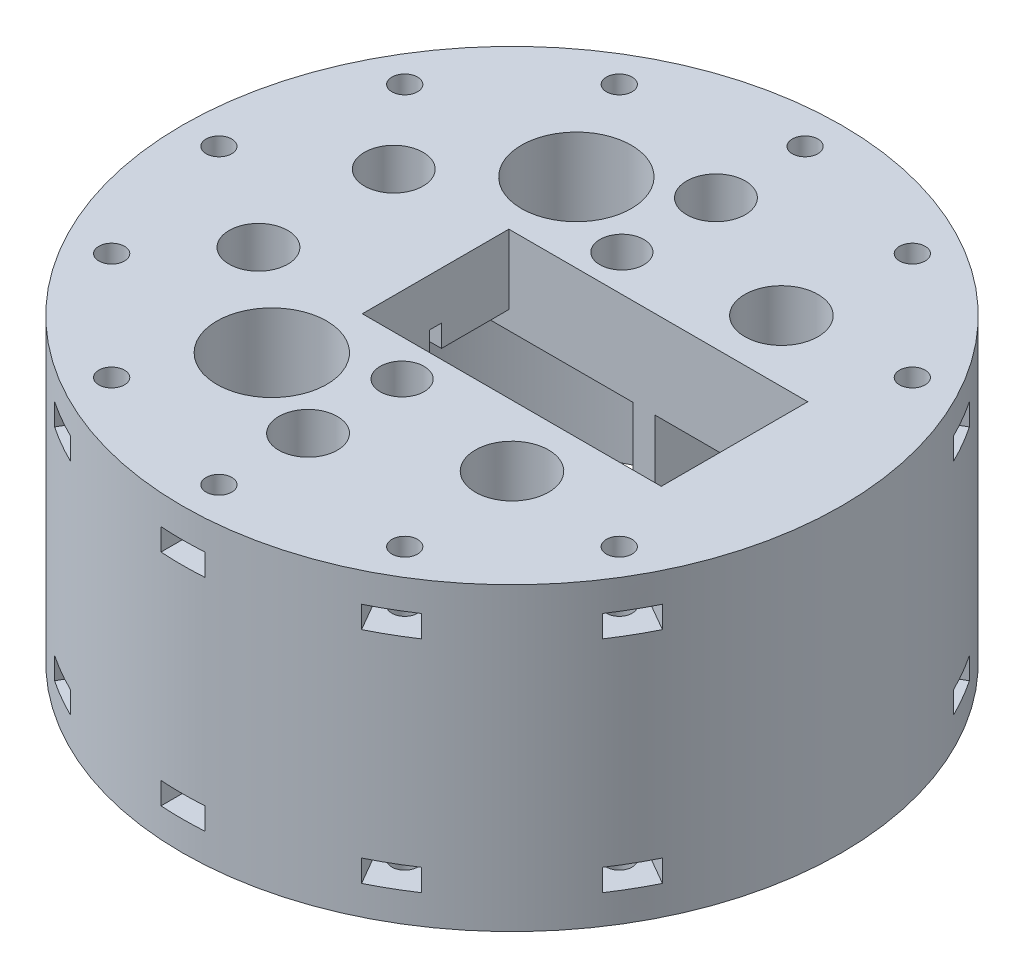
SolidWorks part; units mm, degrees
ref_plane "Front Plane" through (0, 0, 0) normal (0, 0, 1) x (1, 0, 0)
ref_plane "Top Plane" through (0, 0, 0) normal (0, 1, 0) x (1, 0, 0)
ref_plane "Right Plane" through (0, 0, 0) normal (1, 0, 0) x (0, 0, -1)
sketch "Sketch1" plane through (0, 0, 0) normal (0, 1, 0) x (1, 0, 0)
  line L0 (-43.0464, 0) -> (41.9462, 0) construction
  line L1 (0, 43.1152) -> (0, -41.8775) construction
  circle A1 centre (0, 0) radius 45
  dimension "D2" = 90
extrude "Boss-Extrude1" add sketch "Sketch1" along normal blind 41
sketch "Sketch2" plane through (0, 0, 0) normal (0, -1, 0) x (1, 0, 0)
  circle A0 centre (0, 0) radius 35
  dimension "D1" = 70
extrude "Cut-Extrude1" cut sketch "Sketch2" against normal blind 29
sketch "Sketch3" plane through (0, 29, 0) normal (0, -1, 0) x (1, 0, 0)
  line L0 (35, 0) -> (-35, 0) construction
  line L1 (0, -35) -> (0, 35) construction
  line L3 (37.5324, -10) -> (-17.4676, -10)
  line L4 (37.5324, -10) -> (37.5324, 10)
  line L5 (37.5324, 10) -> (-17.4676, 10)
  line L6 (-17.4676, -10) -> (-17.4676, 10)
  circle A0 centre (0, 0) radius 35 construction
  circle A1 centre (0, 0) radius 35 construction
  dimension "D1" = 20
  dimension "D2" = 55
  dimension "D3" = 10
  dimension "D4" = 37.5324
extrude "Cut-Extrude2" cut sketch "Sketch3" against normal blind 2.5 and the other way up to next
sketch "Sketch4" plane through (0, 31.5, 0) normal (0, -1, 0) x (1, 0, 0)
  line L0 (37.5324, 0) -> (-17.4676, 0) construction
  line L1 (37.5324, 10) -> (37.5324, -10) construction
  line L2 (-17.4676, 10) -> (-17.4676, -10) construction
  line L3 (0, -10) -> (0, 10) construction
  line L4 (-17.4676, -10) -> (33.541, -10) construction
  line L5 (33.541, 10) -> (-17.4676, 10) construction
  line L7 (30.3722, -10) -> (-10.4278, -10)
  line L8 (30.3722, -10) -> (30.3722, 10)
  line L9 (30.3722, 10) -> (-10.4278, 10)
  line L10 (-10.4278, -10) -> (-10.4278, 10)
  dimension "D1" = 20
  dimension "D2" = 40.8
  dimension "D3" = 30.3722
  dimension "D4" = 10
extrude "Cut-Extrude3" cut sketch "Sketch4" against normal blind 10.5
sketch "Sketch8" plane through (0, 29, 0) normal (0, -1, 0) x (1, 0, 0)
  line L0 (-17.4676, 0) -> (-35, 0) construction
  line L1 (-17.4676, 10) -> (-17.4676, -10) construction
  line L2 (8.0367, 10) -> (8.0367, 34.0648) construction
  line L3 (33.541, 10) -> (-17.4676, 10) construction
  line L4 (8.0367, -10) -> (8.0367, -29.3194) construction
  line L5 (-17.4676, -10) -> (33.541, -10) construction
  line L6 (6.5367, 10) -> (6.5367, 34.3842)
  line L7 (9.5367, 10) -> (9.5367, 33.6757)
  line L8 (9.5367, 10) -> (6.5367, 10)
  line L9 (9.5367, -10) -> (6.5367, -10)
  line L10 (6.5367, -10) -> (6.5367, -34.3842)
  line L11 (9.5367, -10) -> (9.5367, -33.6757)
  line L12 (-17.4676, 1.5) -> (-34.9678, 1.5)
  line L13 (-17.4676, -1.5) -> (-34.9678, -1.5)
  line L14 (-17.4676, 1.5) -> (-17.4676, -1.5)
  arc A0 (33.541, 10) -> (33.541, -10) centre (0, 0) ccw construction
  arc A1 (9.5367, 33.6757) -> (6.5367, 34.3842) centre (7.9531, 33.6757) ccw
  arc A2 (9.5367, -33.6757) -> (6.5367, -34.3842) centre (7.9531, -33.6757) cw
  arc A3 (-34.9678, 1.5) -> (-34.9678, -1.5) centre (-34.9678, 0) ccw
  dimension "D3" = 1.5
  dimension "D1" = 1.5
  dimension "D2" = 1.5
  dimension "D4" = 1.5
extrude "Boss-Extrude2" add sketch "Sketch8" along normal through all
sketch "Sketch13" plane through (0, 29, 0) normal (0, -1, 0) x (1, 0, 0)
  line L0 (0, 0) -> (0, 35) construction
  line L1 (0, 0) -> (-17.5, 30.3109) construction
  line L2 (0, 0) -> (-41.2446, 0) construction
  line L3 (-32.8892, 11.9707) -> (0, 0) construction
  line L5 (0, 0) -> (24.7487, 24.7487) construction
  arc A0 (6.5367, 34.3842) -> (-34.9678, 1.5) centre (0, 0) ccw construction
  circle A1 centre (-12, 20.7846) radius 7.5
  circle A2 centre (-25.3717, 9.2345) radius 4
  arc A3 (33.541, 10) -> (9.5367, 33.6757) centre (0, 0) ccw construction
  circle A4 centre (18.3848, 18.3848) radius 5
  circle A5 centre (18.3848, -18.3848) radius 5
  circle A6 centre (-12, -20.7846) radius 7.5
  circle A7 centre (-25.3717, -9.2345) radius 4
  circle A8 centre (0, -15) radius 3
  circle A9 centre (0, -27.8351) radius 4
  circle A10 centre (0, 27.8351) radius 4
  circle A11 centre (0, 15) radius 3
  dimension "D3" = 15
  dimension "D6" = 8
  dimension "D8" = 10
  dimension "D10" = 8
  dimension "D11" = 6
  dimension "D1" = 30
  dimension "D2" = 20
  dimension "D4" = 27
  dimension "D5" = 24
  dimension "D7" = 45
  dimension "D9" = 26
  dimension "D12" = 15
extrude "Cut-Extrude7" cut sketch "Sketch13" against normal through all
sketch "Sketch15" plane through (0, 0, -1.5) normal (0, 0, -1) x (-1, 0, 0)
  line L0 (34.9678, 0) -> (17.4676, 29)
  line L1 (17.4676, 29) -> (17.4676, 0)
  line L3 (17.4676, 0) -> (34.9678, 0)
extrude "Cut-Extrude8" cut sketch "Sketch15" against normal blind 3
sketch "Sketch16" plane through (0, 31.5, 0) normal (0, -1, 0) x (1, 0, 0)
  line L0 (-17.4676, 0) -> (37.5324, 0) construction
  line L1 (-17.4676, 10) -> (-17.4676, -10) construction
  line L2 (37.5324, -10) -> (37.5324, 10) construction
  line L3 (30.3722, -0.8) -> (37.5324, -0.8)
  line L4 (-10.4278, -0.8) -> (-17.4676, -0.8)
  line L5 (-10.4278, 10) -> (-10.4278, -10) construction
  line L6 (-10.4278, 0.8) -> (-17.4676, 0.8)
  line L7 (-17.4676, 0.8) -> (-17.4676, -0.8)
  line L8 (-10.4278, 0.8) -> (-10.4278, -0.8)
  line L9 (30.3722, -10) -> (30.3722, 10) construction
  line L10 (30.3722, 0.8) -> (37.5324, 0.8)
  line L11 (37.5324, 0.8) -> (37.5324, -0.8)
  line L12 (30.3722, 0.8) -> (30.3722, -0.8)
  dimension "D1" = 0.8
extrude "Cut-Extrude10" cut sketch "Sketch16" against normal blind 3
sketch "Sketch27" plane through (0, 0, 0) normal (0, -1, 0) x (1, 0, 0)
  line L0 (0, 0) -> (0, -53.17) construction
  line L1 (0, 0) -> (47.7582, -27.5732) construction
  line L3 (31.641, -18.2679) -> (31.641, -21.7321) construction
  line L4 (31.641, -21.7321) -> (34.641, -23.4641) construction
  line L5 (34.641, -23.4641) -> (37.641, -21.7321) construction
  line L6 (37.641, -21.7321) -> (37.641, -18.2679) construction
  line L7 (37.641, -18.2679) -> (34.641, -16.5359) construction
  line L8 (34.641, -16.5359) -> (31.641, -18.2679) construction
  circle A0 centre (0, 0) radius 40 construction
  circle A1 centre (34.641, -20) radius 1.75
  circle A2 centre (0, 0) radius 35 construction
  circle A3 centre (34.641, -20) radius 3 construction
  circle A4 centre (20, -34.641) radius 1.75
  circle A5 centre (0, -40) radius 1.75
  circle A6 centre (-20, -34.641) radius 1.75
  circle A7 centre (-34.641, -20) radius 1.75
  circle A8 centre (-40, 0) radius 1.75
  circle A9 centre (-34.641, 20) radius 1.75
  circle A10 centre (-20, 34.641) radius 1.75
  circle A11 centre (0, 40) radius 1.75
  circle A12 centre (20, 34.641) radius 1.75
  circle A13 centre (34.641, 20) radius 1.75
  circle A15 centre (40, 0) radius 1.75 [skipped]
  point P28 (0, 0)
  point P41 (0, 0)
  dimension "D1" = 80
  dimension "D3" = 3.5
  dimension "D4" = 70
  dimension "D5" = 6
  dimension "D6" = 12
  dimension "D2" = 60
extrude "Cut-Extrude15" cut sketch "Sketch27" against normal through all
ref_plane "Plane1" through (0, 37, 0) normal (0, 1, 0) x (1, 0, 0)
sketch "Sketch28" plane through (0, 37, 0) normal (0, 1, 0) x (1, 0, 0)
  line L0 (0, 0) -> (-54.493, 0) construction
  line L1 (-31.641, 18.2679) -> (-31.641, 21.7321)
  line L2 (-36.5359, 0) -> (-38.2679, 3)
  line L3 (-38.2679, 3) -> (-44.8999, 3)
  line L4 (-31.641, 21.7321) -> (-37.3844, 25.048)
  line L5 (-40.3844, 19.8519) -> (-34.641, 16.5359)
  line L6 (-44.8999, -3) -> (-38.2679, -3)
  line L7 (-38.2679, -3) -> (-36.5359, 0)
  line L8 (-43.4641, 0) -> (-42.5981, -1.5) [skipped]
  line L9 (-41.7321, 3) -> (-42.5981, 1.5) [skipped]
  line L10 (-34.641, 16.5359) -> (-31.641, 18.2679)
  line L11 (-18.2679, 31.641) -> (-16.5359, 34.641)
  line L12 (-16.5359, 34.641) -> (-19.8519, 40.3844)
  line L13 (-25.048, 37.3844) -> (-21.7321, 31.641)
  line L14 (-21.7321, 31.641) -> (-18.2679, 31.641)
  line L15 (0, 36.5359) -> (3, 38.2679)
  line L16 (3, 38.2679) -> (3, 44.8999)
  line L17 (-3, 44.8999) -> (-3, 38.2679)
  line L18 (-3, 38.2679) -> (0, 36.5359)
  line L19 (18.2679, 31.641) -> (21.7321, 31.641)
  line L20 (21.7321, 31.641) -> (25.048, 37.3844)
  line L21 (19.8519, 40.3844) -> (16.5359, 34.641)
  line L22 (16.5359, 34.641) -> (18.2679, 31.641)
  line L23 (31.641, 18.2679) -> (34.641, 16.5359)
  line L24 (34.641, 16.5359) -> (40.3844, 19.8519)
  line L25 (37.3844, 25.048) -> (31.641, 21.7321)
  line L26 (31.641, 21.7321) -> (31.641, 18.2679)
  line L31 (31.641, -18.2679) -> (31.641, -21.7321)
  line L32 (31.641, -21.7321) -> (37.3844, -25.048)
  line L33 (40.3844, -19.8519) -> (34.641, -16.5359)
  line L34 (34.641, -16.5359) -> (31.641, -18.2679)
  line L35 (18.2679, -31.641) -> (16.5359, -34.641)
  line L36 (16.5359, -34.641) -> (19.8519, -40.3844)
  line L37 (25.048, -37.3844) -> (21.7321, -31.641)
  line L38 (21.7321, -31.641) -> (18.2679, -31.641)
  line L39 (0, -36.5359) -> (-3, -38.2679)
  line L40 (-3, -38.2679) -> (-3, -44.8999)
  line L41 (3, -44.8999) -> (3, -38.2679)
  line L42 (3, -38.2679) -> (0, -36.5359)
  line L43 (-18.2679, -31.641) -> (-21.7321, -31.641)
  line L44 (-21.7321, -31.641) -> (-25.048, -37.3844)
  line L45 (-19.8519, -40.3844) -> (-16.5359, -34.641)
  line L46 (-16.5359, -34.641) -> (-18.2679, -31.641)
  line L47 (-31.641, -18.2679) -> (-34.641, -16.5359)
  line L48 (-34.641, -16.5359) -> (-40.3844, -19.8519)
  line L49 (-37.3844, -25.048) -> (-31.641, -21.7321)
  line L50 (-31.641, -21.7321) -> (-31.641, -18.2679)
  line L51 (36.5359, 0) -> (38.2679, -3) [skipped]
  line L52 (38.2679, -3) -> (44.8999, -3) [skipped]
  line L53 (44.8999, 3) -> (38.2679, 3) [skipped]
  line L54 (38.2679, 3) -> (36.5359, 0) [skipped]
  arc A0 (-44.8999, 3) -> (-44.8999, -3) centre (0, 0) ccw
  circle A1 centre (-40, 0) radius 3 construction
  arc A2 (-37.3844, 25.048) -> (-40.3844, 19.8519) centre (0, 0) ccw
  circle A3 centre (-34.641, 20) radius 3 construction
  arc A4 (-19.8519, 40.3844) -> (-25.048, 37.3844) centre (0, 0) ccw
  circle A5 centre (-20, 34.641) radius 3 construction
  arc A6 (3, 44.8999) -> (-3, 44.8999) centre (0, 0) ccw
  circle A7 centre (0, 40) radius 3 construction
  arc A8 (25.048, 37.3844) -> (19.8519, 40.3844) centre (0, 0) ccw
  circle A9 centre (20, 34.641) radius 3 construction
  arc A10 (40.3844, 19.8519) -> (37.3844, 25.048) centre (0, 0) ccw
  circle A11 centre (34.641, 20) radius 3 construction
  arc A14 (37.3844, -25.048) -> (40.3844, -19.8519) centre (0, 0) ccw
  circle A15 centre (34.641, -20) radius 3 construction
  arc A16 (19.8519, -40.3844) -> (25.048, -37.3844) centre (0, 0) ccw
  circle A17 centre (20, -34.641) radius 3 construction
  arc A18 (-3, -44.8999) -> (3, -44.8999) centre (0, 0) ccw
  circle A19 centre (0, -40) radius 3 construction
  arc A20 (-25.048, -37.3844) -> (-19.8519, -40.3844) centre (0, 0) ccw
  circle A21 centre (-20, -34.641) radius 3 construction
  arc A22 (-40.3844, -19.8519) -> (-37.3844, -25.048) centre (0, 0) ccw
  circle A23 centre (-34.641, -20) radius 3 construction
  arc A24 (44.8999, -3) -> (44.8999, 3) centre (0, 0) ccw [skipped]
  circle A25 centre (40, 0) radius 3 construction
  point P94 (0, 0)
  dimension "D1" = 90
  dimension "D2" = 6
  dimension "D3" = 12
extrude "Cut-Extrude17" cut sketch "Sketch28" against normal blind 3
ref_plane "Plane2" through (0, 4, 0) normal (0, -1, 0) x (-1, 0, 0)
sketch "Sketch30" plane through (0, 4, 0) normal (0, -1, 0) x (-1, 0, 0)
  line L0 (0, 0) -> (56.1913, 0) construction
  line L1 (31.641, -18.2679) -> (31.641, -21.7321)
  line L2 (36.5359, 0) -> (38.2679, -3)
  line L3 (38.2679, -3) -> (44.8999, -3)
  line L4 (31.641, -21.7321) -> (37.3844, -25.048)
  line L5 (40.3844, -19.8519) -> (34.641, -16.5359)
  line L6 (44.8999, 3) -> (38.2679, 3)
  line L7 (38.2679, 3) -> (36.5359, 0)
  line L8 (43.4641, 0) -> (42.5981, 1.5) [skipped]
  line L9 (41.7321, -3) -> (42.5981, -1.5) [skipped]
  line L10 (34.641, -16.5359) -> (31.641, -18.2679)
  line L11 (18.2679, -31.641) -> (16.5359, -34.641)
  line L12 (16.5359, -34.641) -> (19.8519, -40.3844)
  line L13 (25.048, -37.3844) -> (21.7321, -31.641)
  line L14 (21.7321, -31.641) -> (18.2679, -31.641)
  line L15 (0, -36.5359) -> (-3, -38.2679)
  line L16 (-3, -38.2679) -> (-3, -44.8999)
  line L17 (3, -44.8999) -> (3, -38.2679)
  line L18 (3, -38.2679) -> (0, -36.5359)
  line L19 (-18.2679, -31.641) -> (-21.7321, -31.641)
  line L20 (-21.7321, -31.641) -> (-25.048, -37.3844)
  line L21 (-19.8519, -40.3844) -> (-16.5359, -34.641)
  line L22 (-16.5359, -34.641) -> (-18.2679, -31.641)
  line L23 (-31.641, -18.2679) -> (-34.641, -16.5359)
  line L24 (-34.641, -16.5359) -> (-40.3844, -19.8519)
  line L25 (-37.3844, -25.048) -> (-31.641, -21.7321)
  line L26 (-31.641, -21.7321) -> (-31.641, -18.2679)
  line L31 (-31.641, 18.2679) -> (-31.641, 21.7321)
  line L32 (-31.641, 21.7321) -> (-37.3844, 25.048)
  line L33 (-40.3844, 19.8519) -> (-34.641, 16.5359)
  line L34 (-34.641, 16.5359) -> (-31.641, 18.2679)
  line L35 (-18.2679, 31.641) -> (-16.5359, 34.641)
  line L36 (-16.5359, 34.641) -> (-19.8519, 40.3844)
  line L37 (-25.048, 37.3844) -> (-21.7321, 31.641)
  line L38 (-21.7321, 31.641) -> (-18.2679, 31.641)
  line L39 (0, 36.5359) -> (3, 38.2679)
  line L40 (3, 38.2679) -> (3, 44.8999)
  line L41 (-3, 44.8999) -> (-3, 38.2679)
  line L42 (-3, 38.2679) -> (0, 36.5359)
  line L43 (18.2679, 31.641) -> (21.7321, 31.641)
  line L44 (21.7321, 31.641) -> (25.048, 37.3844)
  line L45 (19.8519, 40.3844) -> (16.5359, 34.641)
  line L46 (16.5359, 34.641) -> (18.2679, 31.641)
  line L47 (31.641, 18.2679) -> (34.641, 16.5359)
  line L48 (34.641, 16.5359) -> (40.3844, 19.8519)
  line L49 (37.3844, 25.048) -> (31.641, 21.7321)
  line L50 (31.641, 21.7321) -> (31.641, 18.2679)
  line L51 (-36.5359, 0) -> (-38.2679, 3) [skipped]
  line L52 (-38.2679, 3) -> (-44.8999, 3) [skipped]
  line L53 (-44.8999, -3) -> (-38.2679, -3) [skipped]
  line L54 (-38.2679, -3) -> (-36.5359, 0) [skipped]
  arc A0 (44.8999, -3) -> (44.8999, 3) centre (0, 0) ccw
  circle A1 centre (40, 0) radius 3 construction
  arc A2 (37.3844, -25.048) -> (40.3844, -19.8519) centre (0, 0) ccw
  circle A3 centre (34.641, -20) radius 3 construction
  arc A4 (19.8519, -40.3844) -> (25.048, -37.3844) centre (0, 0) ccw
  circle A5 centre (20, -34.641) radius 3 construction
  arc A6 (-3, -44.8999) -> (3, -44.8999) centre (0, 0) ccw
  circle A7 centre (0, -40) radius 3 construction
  arc A8 (-25.048, -37.3844) -> (-19.8519, -40.3844) centre (0, 0) ccw
  circle A9 centre (-20, -34.641) radius 3 construction
  arc A10 (-40.3844, -19.8519) -> (-37.3844, -25.048) centre (0, 0) ccw
  circle A11 centre (-34.641, -20) radius 3 construction
  arc A14 (-37.3844, 25.048) -> (-40.3844, 19.8519) centre (0, 0) ccw
  circle A15 centre (-34.641, 20) radius 3 construction
  arc A16 (-19.8519, 40.3844) -> (-25.048, 37.3844) centre (0, 0) ccw
  circle A17 centre (-20, 34.641) radius 3 construction
  arc A18 (3, 44.8999) -> (-3, 44.8999) centre (0, 0) ccw
  circle A19 centre (0, 40) radius 3 construction
  arc A20 (25.048, 37.3844) -> (19.8519, 40.3844) centre (0, 0) ccw
  circle A21 centre (20, 34.641) radius 3 construction
  arc A22 (40.3844, 19.8519) -> (37.3844, 25.048) centre (0, 0) ccw
  circle A23 centre (34.641, 20) radius 3 construction
  arc A24 (-44.8999, 3) -> (-44.8999, -3) centre (0, 0) ccw [skipped]
  circle A25 centre (-40, 0) radius 3 construction
  point P94 (0, 0)
  dimension "D1" = 90
  dimension "D2" = 6
  dimension "D3" = 12
extrude "Cut-Extrude19" cut sketch "Sketch30" against normal blind 3
